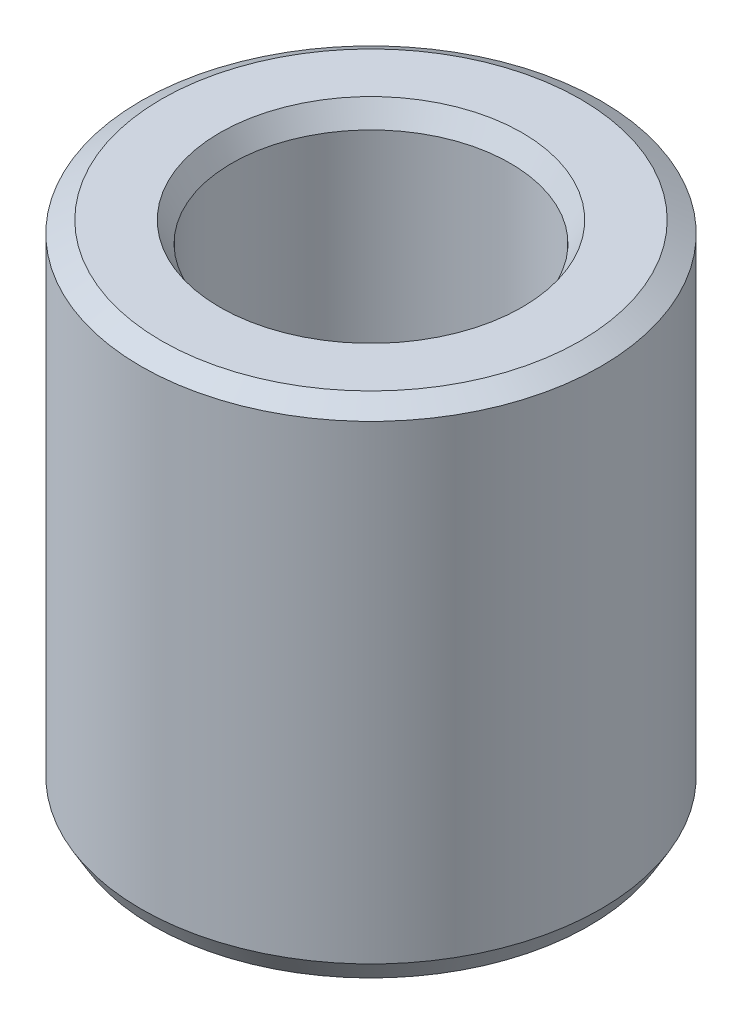
SolidWorks part; units mm, degrees
ref_plane "Front Plane" through (0, 0, 0) normal (0, 0, 1) x (1, 0, 0)
ref_plane "Top Plane" through (0, 0, 0) normal (0, 1, 0) x (1, 0, 0)
ref_plane "Right Plane" through (0, 0, 0) normal (1, 0, 0) x (0, 0, -1)
sketch "Sketch1" plane through (0, 0, 0) normal (0, 1, 0) x (1, 0, 0)
  circle A0 centre (0, 0) radius 17.5
  dimension "SLEEVE_OD" = 35
extrude "Boss-Extrude1" add sketch "Sketch1" along normal blind 38.2202
sketch "Sketch2" plane through (0, 0, 0) normal (0, 1, 0) x (1, 0, 0)
  circle A0 centre (0, 0) radius 10.6012
  dimension "BORE_D" = 21.2023
extrude "Cut-Extrude1" cut sketch "Sketch2" along normal through all
chamfer "Chamfer1" distance 0.901 angle 60 4 edges at (0, 38.2202, 10.6012) (0, 0, 10.6012) (0, 0, 17.5) (0, 38.2202, 17.5) first distance on face at (0, 38.2202, 10.6012) first distance on face at (0, 0, 10.6012) first distance on face at (0, 38.2202, 17.5)
